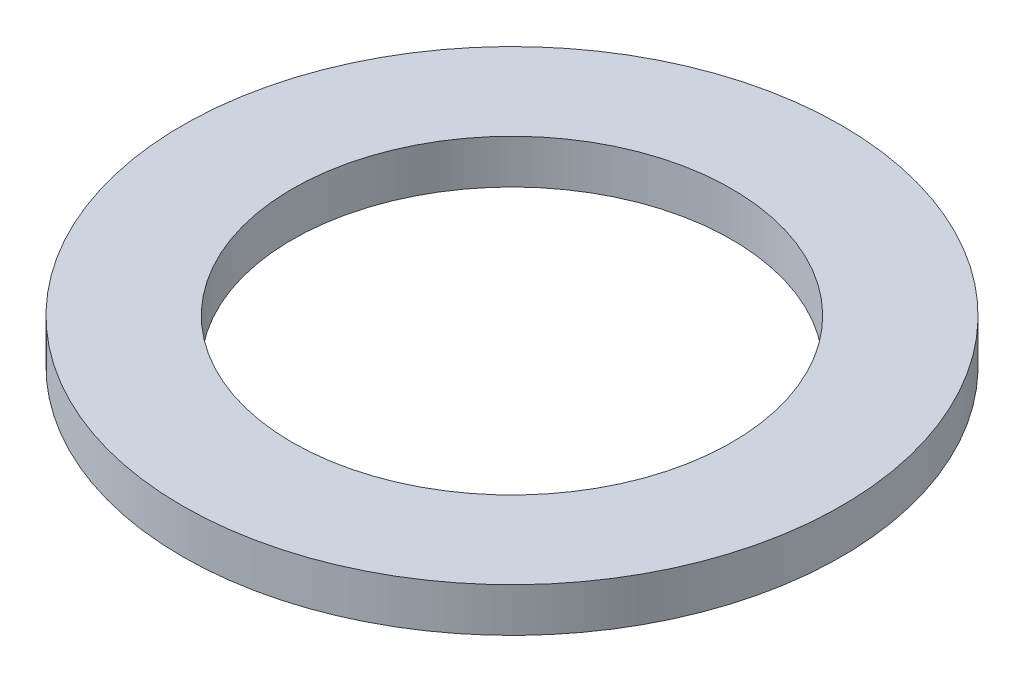
SolidWorks part; units mm, degrees
ref_plane "Front Plane" through (0, 0, 0) normal (0, 0, 1) x (1, 0, 0)
ref_plane "Top Plane" through (0, 0, 0) normal (0, 1, 0) x (1, 0, 0)
ref_plane "Right Plane" through (0, 0, 0) normal (1, 0, 0) x (0, 0, -1)
sketch "Sketch1" plane through (0, 0, 0) normal (0, 1, 0) x (1, 0, 0)
  circle A0 centre (0, 0) radius 45
  dimension "FLANGE_OD" = 90
extrude "Boss-Extrude1" add sketch "Sketch1" along normal blind 6
sketch "Sketch2" plane through (0, 0, 0) normal (0, 1, 0) x (1, 0, 0)
  circle A0 centre (0, 0) radius 30
  dimension "BORE_D" = 60
extrude "Cut-Extrude1" cut sketch "Sketch2" along normal through all
sketch "Sketch3" plane through (0, 6, 0) normal (0, 1, 0) x (1, 0, 0)
  circle A0 centre (0, 0) radius 19.2689 construction
  circle A1 centre (-19.2689, 0) radius 2.664
  dimension "BOLT_D" = 5.328
  dimension "BOLT_PCD" = 38.5378
extrude "Cut-Extrude2" cut sketch "Sketch3" against normal blind 5.4173 rebuild error yes
pattern_circular "CirPattern1" count 6 over 360 rebuild error yes
